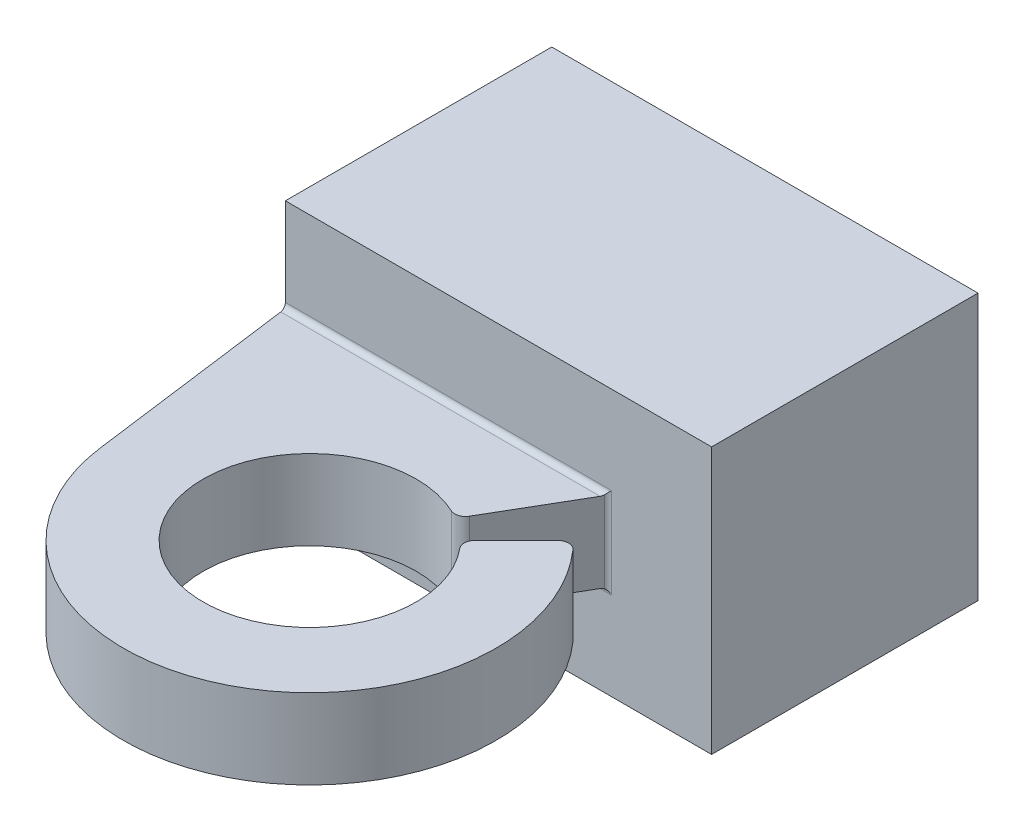
SolidWorks part; units mm, degrees
ref_plane "前视基准面" through (0, 0, 0) normal (0, 0, 1) x (1, 0, 0)
ref_plane "上视基准面" through (0, 0, 0) normal (0, 1, 0) x (1, 0, 0)
ref_plane "右视基准面" through (0, 0, 0) normal (1, 0, 0) x (0, 0, -1)
sketch "草图1" plane through (0, 0, 0) normal (1, 0, 0) x (0, 0, -1)
  line L0 (0, 0) -> (11989.1422, 0) construction
  line L1 (0, 0) -> (0, 11989.1422) construction
  line L3 (-2.5, -2.5) -> (2.5, -2.5)
  line L4 (-2.5, -2.5) -> (-2.5, 2.5)
  line L5 (-2.5, 2.5) -> (2.5, 2.5)
  line L6 (2.5, -2.5) -> (2.5, 2.5)
  line L7 (-2.5, -2.5) -> (2.5, 2.5) construction
  line L8 (-2.5, 2.5) -> (2.5, -2.5) construction
  point P5 (0, 0)
  dimension "D1" = 5
  dimension "D2" = 5
extrude "凸台-拉伸1" add sketch "草图1" along normal blind 8
sketch "草图2" plane through (0, 0, 0) normal (-1, 0, 0) x (0, 0, 1)
  circle A0 centre (0, 0) radius 2
  dimension "D1" = 4
sketch "草图3" plane through (0, 2.5, 0) normal (0, 1, 0) x (1, 0, 0)
  line L0 (0, 0) -> (8, 0) construction
  line L1 (8, 2.5) -> (8, -2.5) construction
  line L3 (1.5, 0.2) -> (6.5, 0.2)
  line L4 (1.5, 0.2) -> (1.5, -0.2)
  line L5 (1.5, -0.2) -> (6.5, -0.2)
  line L6 (6.5, 0.2) -> (6.5, -0.2)
  line L7 (1.5, 0.2) -> (6.5, -0.2) construction
  line L8 (1.5, -0.2) -> (6.5, 0.2) construction
  point P5 (4, 0)
  dimension "D1" = 5
  dimension "D2" = 0.4
sketch "草图4" plane through (0, 0, 0) normal (0, 1, 0) x (1, 0, 0)
  line L0 (4, -2.5) -> (4, -6.0432) construction
  line L1 (8, -2.5) -> (0, -2.5) construction
  line L2 (0, -2.5) -> (0.5303, -6.5029)
  line L3 (5.007, -4.3152) -> (6.0647, -2.5)
  line L4 (5.4142, -4.629) -> (6.4749, -3.5683)
  line L5 (4, -6.0432) -> (15.0688, -6.0432) construction
  line L6 (0, -2.5) -> (6.0647, -2.5)
  arc A0 (0.5303, -6.5029) -> (6.4749, -3.5683) centre (4, -6.0432) ccw
  arc A1 (5.007, -4.3152) -> (5.4142, -4.629) centre (4, -6.0432) ccw
  dimension "D1" = 7
  dimension "D2" = 4
  dimension "D3" = 45
extrude "凸台-拉伸3" add sketch "草图4" along normal mid plane 1.5
fillet "圆角2" radius 0.2 2 edges at (6.4749, 0, 3.5683) (5.4142, 0, 4.629)
fillet "圆角3" radius 0.2 1 edges at (5.007, 0, 4.3152)
sketch "草图5" plane through (0, 0, 0) normal (-1, 0, 0) x (0, 0, 1)
  line L1 (-2, -2) -> (2, -2)
  line L2 (-2, -2) -> (-2, 2)
  line L3 (-2, 2) -> (2, 2)
  line L4 (2, -2) -> (2, 2)
  line L5 (-2, -2) -> (2, 2) construction
  line L6 (-2, 2) -> (2, -2) construction
  point P0 (0, 0)
  dimension "D1" = 4
  dimension "D2" = 4
extrude "切除-拉伸1" cut sketch "草图5" against normal blind 7
sketch "草图6" plane through (0, 2.5, 0) normal (0, 1, 0) x (1, 0, 0)
  line L0 (4, 0) -> (4, 1.635) construction
  line L1 (0, 0) -> (7.6634, 0) construction
  line L6 (0, 0) -> (8, 0) construction
  line L8 (1, -0.15) -> (1, 0.15)
  line L9 (1, 0.15) -> (7, 0.15)
  line L10 (7, -0.15) -> (7, 0.15)
  line L11 (4, 0) -> (7, 0.15) construction
  line L12 (1, 0.15) -> (7, -0.15) construction
  line L13 (1, -0.15) -> (7, -0.15)
  line L14 (1, 1.3557) -> (7, 1.3557)
  line L15 (1, 1.3557) -> (1, 1.0557)
  line L16 (1, 1.0557) -> (7, 1.0557)
  line L17 (7, 1.3557) -> (7, 1.0557)
  line L18 (1, 1.3557) -> (7, 1.0557) construction
  line L19 (1, 1.0557) -> (7, 1.3557) construction
  line L20 (1, -1.3557) -> (1, -1.0557)
  line L21 (7, -1.3557) -> (7, -1.0557)
  line L22 (1, -1.0557) -> (7, -1.0557)
  line L23 (1, -1.3557) -> (7, -1.3557)
  point P8 (4, 1.2057)
  point P18 (7, 0)
  point P19 (1, 0)
  dimension "D1" = 0.3
  dimension "D3" = 0.3
  dimension "D4" = 6
extrude "凸台-拉伸4" add sketch "草图6" against normal blind 0.6
fillet "圆角4" radius 0.1 9 edges at (1, 1.9, 1.2057) (4, 1.9, 1.3557) (4, 1.9, 1.0557) (1, 1.9, 0) (4, 1.9, 0.15) (4, 1.9, -0.15) (1, 1.9, -1.2057) (4, 1.9, -1.0557) (4, 1.9, -1.3557)
mirror "镜向1" about plane through (0, 0, 0) normal (0, 1, 0) of "圆角4", "凸台-拉伸4"
fillet "圆角5" radius 0.1 3 edges at (3.0324, -0.75, 2.5) (3.0324, 0.75, 2.5) (6.0647, 0, 2.5)
